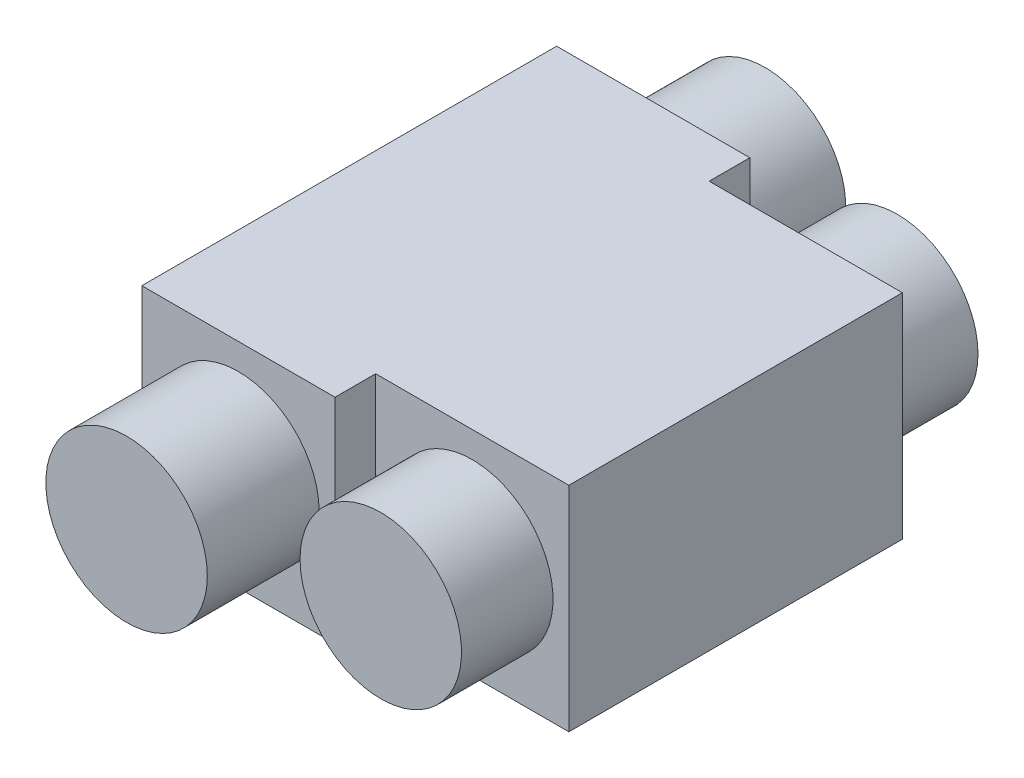
SolidWorks part; units mm, degrees
other "标注1"
sketch "草图6" plane through (-95, 0, 157) normal (0, 0, 1) x (1, 0, 0)
ref_plane "前视基准面" through (0, 0, 0) normal (0, 0, 1) x (1, 0, 0)
ref_plane "上视基准面" through (0, 0, 0) normal (0, 1, 0) x (1, 0, 0)
ref_plane "右视基准面" through (0, 0, 0) normal (1, 0, 0) x (0, 0, -1)
other "质心 (COM)"
sketch "草图1" plane through (0, 0, 0) normal (0, 1, 0) x (1, 0, 0)
  line L0 (-95, -102) -> (0, -102)
  line L1 (-95, -82) -> (95, -82)
  line L2 (-95, -82) -> (-95, 82)
  line L3 (-95, 82) -> (95, 82)
  line L4 (95, -82) -> (95, 82)
  line L5 (-95, -82) -> (95, 82) construction
  line L6 (-95, 82) -> (95, -82) construction
  line L7 (-95, -102) -> (-95, 102)
  line L8 (0, -102) -> (0, 102)
  line L9 (-95, 102) -> (0, 102)
  point P0 (0, 0)
  point P6 (-95, 0)
  dimension "D1" = 190
  dimension "D2" = 164
  dimension "D3" = 204
  dimension "D4" = 102
  dimension "D5" = 95
extrude "凸台-拉伸2" add sketch "草图1" along normal blind 105 contours L4 L3 L2 L1
extrude "凸台-拉伸3" add sketch "草图1<5>" along normal blind 105 contours L0 L8 L9 L7
sketch "草图1<5>" plane through (0, 0, 0) normal (0, 1, 0) x (1, 0, 0) same geometry as "草图1"
sketch "草图2" plane through (0, 0, 102) normal (0, 0, 1) x (1, 0, 0)
  line L0 (-95, 105) -> (-95, 0) construction
  line L1 (-95, 0) -> (0, 0) construction
  circle A0 centre (-47.5, 52.5) radius 39.7
  dimension "D2" = 79.4
  dimension "D1" = 47.5
  dimension "D3" = 52.5
extrude "凸台-拉伸4" add sketch "草图2" along normal blind 55
sketch "草图3" plane through (0, 0, 82) normal (0, 0, 1) x (1, 0, 0)
  line L0 (95, 105) -> (95, 0) construction
  line L1 (0, 0) -> (95, 0) construction
  circle A0 centre (47.5, 52.5) radius 39.7
  dimension "D2" = 79.4
  dimension "D1" = 47.5
  dimension "D3" = 52.5
extrude "凸台-拉伸5" add sketch "草图3" along normal blind 45
sketch "草图4" plane through (0, 0, -102) normal (0, 0, -1) x (-1, 0, 0)
  line L0 (95, 105) -> (95, 0) construction
  line L1 (95, 0) -> (0, 0) construction
  circle A0 centre (47.5, 52.5) radius 39.7
  dimension "D2" = 79.4
  dimension "D1" = 47.5
  dimension "D3" = 52.5
extrude "凸台-拉伸6" add sketch "草图4" along normal blind 55
sketch "草图5" plane through (0, 0, -82) normal (0, 0, -1) x (-1, 0, 0)
  line L0 (-95, 105) -> (-95, 0) construction
  line L1 (0, 0) -> (-95, 0) construction
  circle A0 centre (-47.5, 52.5) radius 39.7
  dimension "D2" = 79.4
  dimension "D1" = 47.5
  dimension "D3" = 52.5
extrude "凸台-拉伸7" add sketch "草图5" along normal blind 45
